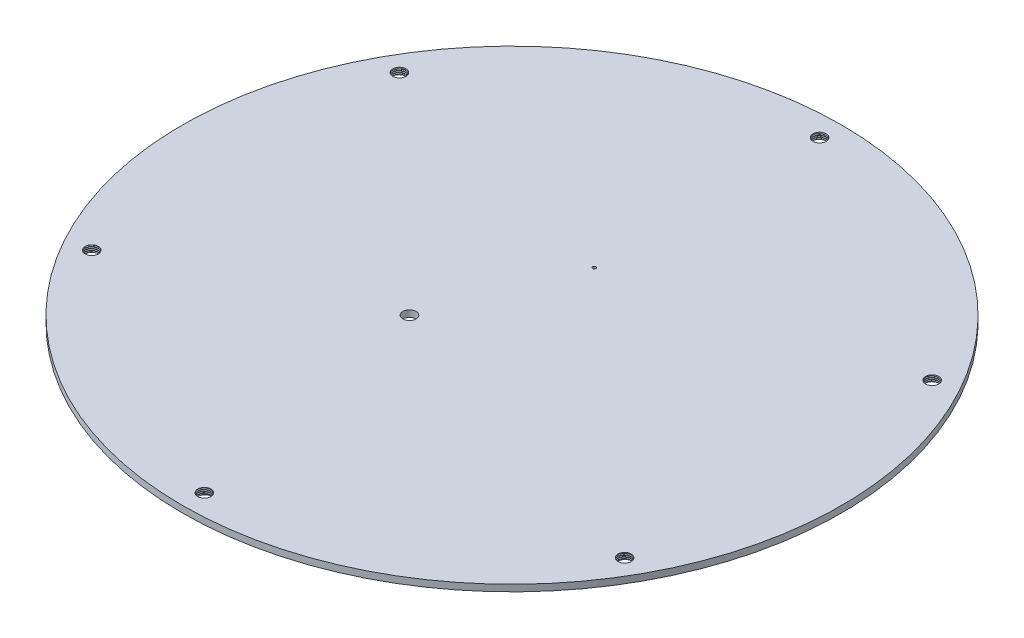
SolidWorks part; units mm, degrees
material "1060 Alloy"
ref_plane "Front Plane" through (0, 0, 0) normal (0, 0, 1) x (1, 0, 0)
ref_plane "Top Plane" through (0, 0, 0) normal (0, 1, 0) x (1, 0, 0)
ref_plane "Right Plane" through (0, 0, 0) normal (1, 0, 0) x (0, 0, -1)
sketch "Sketch1" plane through (0, 0, 0) normal (0, 1, 0) x (1, 0, 0)
  circle A0 centre (0, 0) radius 50
  circle A1 centre (0, 46.67) radius 1
  circle A2 centre (40.4174, 23.335) radius 1
  circle A3 centre (40.4174, -23.335) radius 1
  circle A4 centre (0, -46.67) radius 1
  circle A5 centre (-40.4174, -23.335) radius 1
  circle A6 centre (-40.4174, 23.335) radius 1
  point P17 (0, 0)
  dimension "D1" = 100
  dimension "D2" = 2
  dimension "D3" = 46.67
  dimension "D4" = 6
extrude "Boss-Extrude1" add sketch "Sketch1" along normal blind 1
thread "Thread1" pitch 0.25 method cut profile "Thread Profile1" start angle 0, offset 0, length 10, pitch 0.25, diameter 2
ref_plane "Plane1" through (-41.4174, 1, 23.335) normal (0, 0, 1) x (-1, 0, 0)
sketch "Thread Profile1" plane through (-41.4174, 1, 23.335) normal (0, 0, 1) x (-1, 0, 0)
  line L0 (0, 0) -> (0, 0.25) construction
  line L1 (0, 0) -> (0.1353, 0.0781)
  line L2 (0.1353, 0.0781) -> (0.1353, 0.1094)
  line L3 (0.1353, 0.1094) -> (0, 0.1875)
  line L4 (0.1353, 0.0937) -> (0, 0.0937) construction
  line L11 (0, 0) -> (0, 0.1875)
  point P2 (0, 0)
  dimension "Pitch" = 0.25
  dimension "Profile_Angle" = 60
  dimension "Profile_Land" = 0.0312
  dimension "Profile_Height" = 0.1353
pattern_circular "CirPattern1" count 6 over 360 about axis through (0, 0, 0) along (0, 1, 0) of "Thread1"
sketch "Sketch2" plane through (0, 1, 0) normal (0, 1, 0) x (1, 0, 0)
  line L0 (0, 0) -> (0, 12.5) construction
  line L1 (0, 12.5) -> (0, 0) construction
  line L2 (0, 0) -> (-20.5223, -20.5223) construction
  circle A0 centre (0, 12.5) radius 0.25
  circle A1 centre (-7.7782, -7.7782) radius 1
  dimension "D1" = 0.5
  dimension "D3" = 2
  dimension "D2" = 12.5
  dimension "D4" = 11
extrude "Cut-Extrude1" cut sketch "Sketch2" against normal through all both and the other way through all
